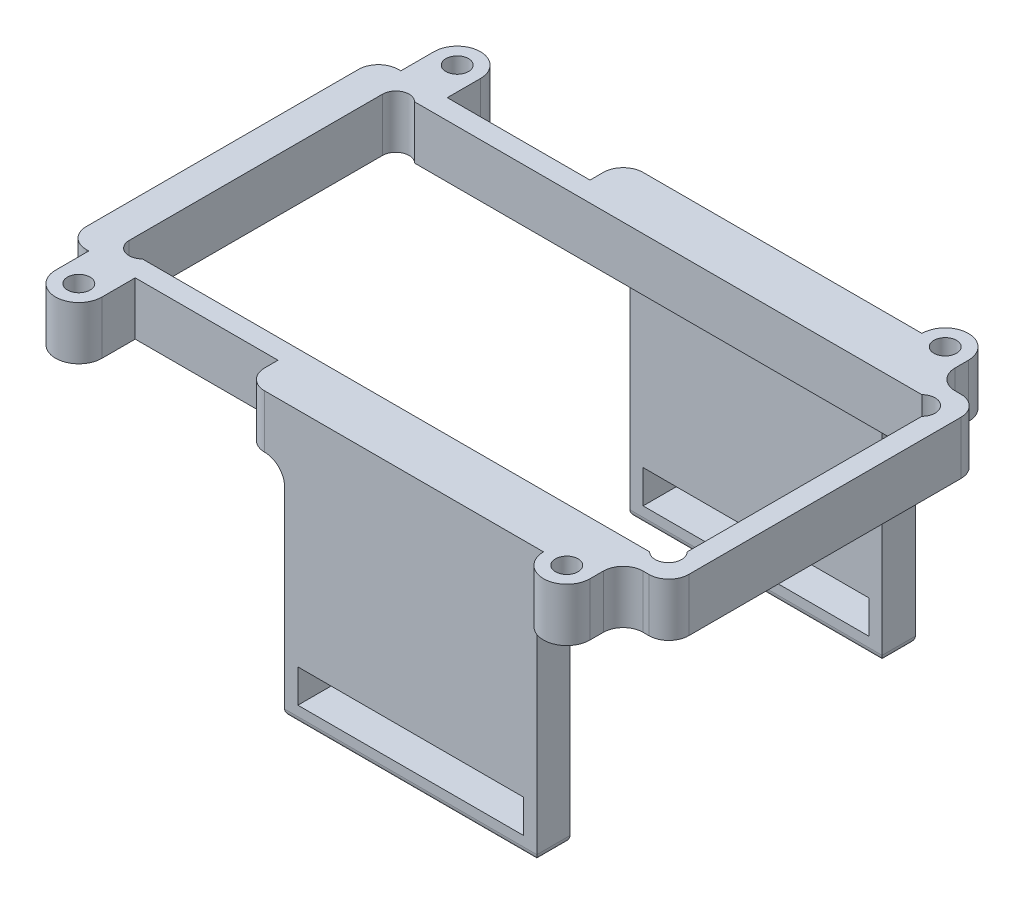
SolidWorks part; units mm, degrees
material "AISI 1035 钢 (SS)"
ref_plane "前视基准面" through (0, 0, 0) normal (0, 0, 1) x (1, 0, 0)
ref_plane "上视基准面" through (0, 0, 0) normal (0, 1, 0) x (1, 0, 0)
ref_plane "右视基准面" through (0, 0, 0) normal (1, 0, 0) x (0, 0, -1)
sketch "草图1" plane through (0, 0, 0) normal (0, 1, 0) x (1, 0, 0)
  line L0 (-34.1716, -20.5) -> (36, -20.5)
  line L1 (-38, 23.5) -> (40, 23.5)
  line L2 (-40, 21.5) -> (-40, -21.5)
  line L3 (-38, -23.5) -> (40, -23.5)
  line L4 (40, 23.5) -> (40, -23.5)
  line L5 (-40, 23.5) -> (40, -23.5) construction
  line L6 (-40, -23.5) -> (40, 23.5) construction
  line L7 (-37, -20.5) -> (37, -20.5) construction
  line L8 (-34.1716, 20.5) -> (36, 20.5)
  line L9 (-37, 17.6716) -> (-37, -17.6716)
  line L10 (37, 20.5) -> (37, -20.5) construction
  line L11 (-6.6939, 3.9327) -> (38, -20.5) construction
  line L12 (-6.6939, -3.9327) -> (0.5, 0) construction
  line L13 (38, -18.5) -> (38, 18.5)
  line L14 (-37, 20.5) -> (37, 20.5) construction
  line L15 (-37, -20.5) -> (-35.5858, -19.0858) construction
  line L16 (0, 0) -> (-3.1731, 0) construction
  line L17 (-37, 20.5) -> (-37, -20.5) construction
  line L18 (-40, -23.5) -> (40, -23.5) construction
  line L19 (-40, 23.5) -> (-40, -23.5) construction
  line L20 (-40, 23.5) -> (40, 23.5) construction
  arc A0 (36, -20.5) -> (38, -18.5) centre (36, -18.5) ccw
  arc A1 (38, 18.5) -> (36, 20.5) centre (36, 18.5) ccw
  arc A2 (-37, -17.6716) -> (-34.1716, -20.5) centre (-35.5858, -19.0858) ccw
  arc A3 (-37, 17.6716) -> (-34.1716, 20.5) centre (-35.5858, 19.0858) cw
  arc A4 (-38, -23.5) -> (-40, -21.5) centre (-38, -21.5) cw
  arc A5 (-38, 23.5) -> (-40, 21.5) centre (-38, 21.5) ccw
  point P0 (0, 0)
  point P16 (38, 20.5)
  dimension "D5" = 2
  dimension "D8" = 4
  dimension "D9" = 2
  dimension "D1" = 80
  dimension "D2" = 47
  dimension "D4" = 2
  dimension "D6" = 45
  dimension "D7" = 2
  dimension "D3" = 3
extrude "凸台-拉伸1" add sketch "草图1" along normal blind 23.5
sketch "草图2" plane through (0, 0, 0) normal (0, -1, 0) x (1, 0, 0)
  line L0 (1, 23.5) -> (1, -23.5) construction
  line L1 (-38, 23.5) -> (40, 23.5) construction
  line L2 (40, -23.5) -> (-38, -23.5) construction
  line L3 (37.75, 0) -> (-35.75, 0) construction
  line L4 (37.75, 28.5) -> (37.75, -28.5) construction
  line L5 (40, 0) -> (55, 0) construction
  line L6 (40, 23.5) -> (40, -23.5) construction
  line L7 (55, 0) -> (-46, 0) construction
  line L9 (48.125, 23.5) -> (41.25, 23.5)
  line L11 (-42.625, -23.5) -> (-39.25, -23.5)
  line L13 (-34.1716, 20.5) -> (36, 20.5) construction
  line L14 (5.4444, -0.4555) -> (5.4444, 0.4555) construction
  line L15 (-34.1716, 20.5) -> (42.2319, 20.5)
  line L16 (34.25, 23.5) -> (-32.25, 23.5)
  line L17 (42.2319, -20.5) -> (-34.1716, -20.5)
  line L18 (47, -20.5) -> (-38, 20.5) construction
  line L19 (47, 20.5) -> (-38, -20.5) construction
  line L20 (37.75, 18.5) -> (37.75, 28.5) construction
  line L21 (34.25, 23.5) -> (34.25, 28.5)
  line L22 (41.25, -23.5) -> (41.25, -28.5)
  line L23 (41.25, 23.5) -> (41.25, 28.5)
  line L24 (34.25, -23.5) -> (34.25, -28.5)
  line L25 (-32.25, -23.5) -> (-32.25, -28.5)
  line L26 (-39.25, -23.5) -> (-39.25, -28.5)
  line L27 (-39.25, 23.5) -> (-39.25, 28.5)
  line L28 (-32.25, 23.5) -> (-32.25, 28.5)
  line L29 (-37, -17.6716) -> (-37, 17.6716)
  line L30 (45.0603, -14.2439) -> (-37, -14.2439) construction
  line L31 (4.0302, -14.2439) -> (4.0302, -22.3158) construction
  line L32 (45.0603, 17.6716) -> (45.0603, -17.6716)
  line L33 (41.25, -23.5) -> (48.125, -23.5)
  line L34 (-32.25, -23.5) -> (34.25, -23.5)
  line L35 (-39.25, 23.5) -> (-42.625, 23.5)
  line L36 (-42.625, 23.5) -> (-42.625, -23.5)
  line L37 (48.125, 23.5) -> (48.125, -23.5)
  circle A0 centre (37.75, 28.5) radius 1.7
  arc A1 (41.25, -28.5) -> (34.25, -28.5) centre (37.75, -28.5) cw
  arc A2 (41.25, 28.5) -> (34.25, 28.5) centre (37.75, 28.5) ccw
  circle A3 centre (37.75, -28.5) radius 1.7
  arc A4 (-39.25, -28.5) -> (-32.25, -28.5) centre (-35.75, -28.5) ccw
  circle A5 centre (-35.75, -28.5) radius 1.7
  arc A6 (-39.25, 28.5) -> (-32.25, 28.5) centre (-35.75, 28.5) cw
  circle A7 centre (-35.75, 28.5) radius 1.7
  arc A8 (-37, -17.6716) -> (-34.1716, -20.5) centre (-35.5858, -19.0858) ccw construction
  arc A9 (-34.1716, 20.5) -> (-37, 17.6716) centre (-35.5858, 19.0858) ccw construction
  arc A10 (-37, -17.6716) -> (-34.1716, -20.5) centre (-35.5858, -19.0858) ccw
  arc A11 (-34.1716, 20.5) -> (-37, 17.6716) centre (-35.5858, 19.0858) ccw
  arc A12 (42.2319, 20.5) -> (45.0603, 17.6716) centre (43.6461, 19.0858) cw
  arc A13 (45.0603, -17.6716) -> (42.2319, -20.5) centre (43.6461, -19.0858) cw
  point P6 (1, 0)
  point P18 (4.5, 0)
  point P31 (37.75, 23.5)
  dimension "D3" = 3.4
  dimension "D1" = 73.5
  dimension "D2" = 57
  dimension "D4" = 15
  dimension "D5" = 101
  dimension "D6" = 85
extrude "凸台-拉伸2" add sketch "草图2" along normal blind 8
sketch "草图4" plane through (-40, 0, 0) normal (-1, 0, 0) x (0, 0, 1)
  line L0 (0, 0) -> (0, 20.5) construction
  line L3 (-21.5, 0) -> (21.5, 0) construction
  line L4 (-21.5, 23.5) -> (21.5, 23.5) construction
  line L6 (17, 0) -> (-17, 0)
  line L7 (20, 3) -> (20, 17.5)
  line L8 (17, 20.5) -> (-17, 20.5)
  line L9 (-20, 3) -> (-20, 17.5)
  line L10 (20, 0) -> (-20, 20.5) construction
  line L11 (20, 20.5) -> (-20, 0) construction
  arc A0 (-17, 0) -> (-20, 3) centre (-17, 3) cw
  arc A1 (-20, 17.5) -> (-17, 20.5) centre (-17, 17.5) cw
  arc A2 (17, 20.5) -> (20, 17.5) centre (17, 17.5) cw
  arc A3 (17, 0) -> (20, 3) centre (17, 3) ccw
  point P6 (0, 11.75)
  point P7 (0, 10.25)
  dimension "D3" = 3
  dimension "D1" = 3
  dimension "D2" = 40
extrude "切除-拉伸1" cut sketch "草图4" against normal up to next
sketch "草图5" plane through (0, 0, -23.5) normal (0, 0, -1) x (-1, 0, 0)
  line L0 (-1, 23.5) -> (-1, 19.5) construction
  line L1 (-40, 23.5) -> (38, 23.5) construction
  line L2 (-40, 11.75) -> (-37, 11.75) construction
  line L3 (-40, 23.5) -> (-40, 0) construction
  line L4 (-37, 11.75) -> (-37, 17.5)
  line L5 (-35, 19.5) -> (33, 19.5)
  line L6 (38, 23.5) -> (38, 0) construction
  line L7 (-37, 11.75) -> (-37, 6)
  line L8 (-35, 4) -> (33, 4)
  line L9 (35, 6) -> (35, 17.5)
  arc A0 (-37, 6) -> (-35, 4) centre (-35, 6) ccw
  arc A1 (-37, 17.5) -> (-35, 19.5) centre (-35, 17.5) cw
  arc A2 (33, 19.5) -> (35, 17.5) centre (33, 17.5) cw
  arc A3 (33, 4) -> (35, 6) centre (33, 6) ccw
  point P16 (-37, 4)
  point P21 (35, 19.5)
  dimension "D5" = 2
  dimension "D1" = 4
  dimension "D2" = 3
  dimension "D3" = 3
  dimension "D4" = 7.75
extrude "切除-拉伸2" cut sketch "草图5" against normal up to surface (47 mm away) up to face at (1, 3.875, 23.5)
sketch "草图6" plane through (40, 0, 0) normal (1, 0, 0) x (0, 0, -1)
  line L0 (0, 23.5) -> (0, 20.5) construction
  line L1 (-23.5, 23.5) -> (23.5, 23.5) construction
  line L2 (23.5, 11.75) -> (21, 11.75) construction
  line L3 (23.5, 23.5) -> (23.5, 0) construction
  line L4 (21, 5) -> (21, 18.5)
  line L5 (19, 20.5) -> (-19, 20.5)
  line L6 (0, 20.5) -> (0, 7.2335) construction
  line L7 (-21, 5) -> (-21, 18.5)
  line L9 (0, 3) -> (0, 0) construction
  line L10 (-20.5, 0) -> (20.5, 0) construction
  line L13 (16, 0) -> (-16, 0)
  line L15 (-21, 5) -> (-21, 0)
  line L16 (-23.5, 0) -> (-20.5, 0) construction
  line L17 (-21, 0) -> (-16, 0)
  line L18 (21, 5) -> (21, 0)
  line L19 (23.5, 0) -> (20.5, 0) construction
  line L20 (21, 0) -> (16, 0)
  arc A0 (-21, 18.5) -> (-19, 20.5) centre (-19, 18.5) cw
  arc A1 (19, 20.5) -> (21, 18.5) centre (19, 18.5) cw
  point P14 (-21, 11.75)
  point P17 (-21, 20.5)
  point P20 (21, 20.5)
  point P23 (-21, 3)
  point P26 (21, 3)
  point P37 (-16, 3)
  dimension "D3" = 2
  dimension "D1" = 3
  dimension "D2" = 2.5
extrude "切除-拉伸3" cut sketch "草图6" against normal up to next
sketch "草图9" plane through (0, 0, 23.5) normal (0, 0, 1) x (1, 0, 0)
  line L0 (34.25, -8) -> (34.25, 0)
  line L1 (34.25, 0) -> (-10.75, 0)
  line L2 (-10.75, 0) -> (-10.75, -8)
  line L3 (34.25, -8) -> (-32.25, -8) construction
  line L4 (-10.75, -8) -> (34.25, -8)
  dimension "D1" = 45
extrude "凸台-拉伸3" add sketch "草图9" along normal blind 5
sketch "草图10" plane through (0, 0, -23.5) normal (0, 0, -1) x (-1, 0, 0)
  line L0 (-34.25, -8) -> (10.75, -8)
  line L1 (32.25, -8) -> (-34.25, -8) construction
  line L2 (-34.25, -8) -> (-34.25, 0)
  line L3 (-34.25, 0) -> (10.75, 0)
  line L4 (10.75, 0) -> (10.75, -8)
  dimension "D1" = 45
extrude "凸台-拉伸4" add sketch "草图10" along normal blind 5
sketch "草图11" plane through (0, -8, 0) normal (0, -1, 0) x (1, 0, 0)
  line L0 (-10.75, 28.5) -> (34.25, 28.5) construction
  line L1 (-4.75, 28.5) -> (33.25, 28.5)
  line L2 (-4.75, 28.5) -> (-4.75, 23.5)
  line L3 (-4.75, 23.5) -> (33.25, 23.5)
  line L4 (33.25, 28.5) -> (33.25, 23.5)
  line L5 (-10.75, 28.5) -> (-10.75, 23.5) construction
  dimension "D1" = 5
  dimension "D2" = 38
  dimension "D3" = 6
extrude "凸台-拉伸5" add sketch "草图11" along normal blind 33
sketch "草图12" plane through (0, 0, 23.5) normal (0, 0, -1) x (-1, 0, 0)
  line L0 (4.75, -41) -> (-33.25, -41) construction
  line L1 (-31.25, -38.5) -> (2.75, -38.5)
  line L2 (-31.25, -38.5) -> (-31.25, -33.5)
  line L3 (-31.25, -33.5) -> (2.75, -33.5)
  line L4 (2.75, -38.5) -> (2.75, -33.5)
  line L5 (-31.25, -38.5) -> (2.75, -33.5) construction
  line L6 (-31.25, -33.5) -> (2.75, -38.5) construction
  line L7 (-33.25, -41) -> (-33.25, -8) construction
  point P0 (-14.25, -36)
  dimension "D1" = 5
  dimension "D2" = 5
  dimension "D3" = 34
  dimension "D4" = 2
extrude "切除-拉伸4" cut sketch "草图12" against normal blind 5
mirror "镜向1" about plane through (0, 0, 0) normal (0, 0, 1) of "切除-拉伸4", "凸台-拉伸5"
sketch "草图13" plane through (0, 23.5, 0) normal (0, 1, 0) x (1, 0, 0)
  line L0 (-38, 23.5) -> (40, 23.5)
  line L1 (40, 23.5) -> (40, -23.5)
  line L2 (40, -23.5) -> (-38, -23.5)
  line L3 (38, 18.5) -> (38, -18.5)
  line L4 (-40, -21.5) -> (-40, 21.5)
  line L5 (-34.1716, 20.5) -> (36, 20.5)
  line L6 (-37, 17.6716) -> (-37, -17.6716)
  line L7 (-34.1716, -20.5) -> (36, -20.5)
  arc A0 (-40, 21.5) -> (-38, 23.5) centre (-38, 21.5) cw
  arc A1 (-40, -21.5) -> (-38, -23.5) centre (-38, -21.5) ccw
  arc A2 (38, 18.5) -> (36, 20.5) centre (36, 18.5) ccw
  arc A3 (36, -20.5) -> (38, -18.5) centre (36, -18.5) ccw
  arc A4 (-37, -17.6716) -> (-34.1716, -20.5) centre (-35.5858, -19.0858) ccw
  arc A6 (-34.1716, 20.5) -> (-37, 17.6716) centre (-35.5858, 19.0858) ccw
extrude "切除-拉伸5" cut sketch "草图13" against normal blind 23.5
sketch "草图14" plane through (0, -8, 0) normal (0, -1, 0) x (1, 0, 0)
  line L0 (-37.5858, 19.0858) -> (-37.5858, -19.0858)
  line L1 (-37, 17.6716) -> (-37, -17.6716)
  arc A0 (-34.1716, 20.5) -> (-37, 17.6716) centre (-35.5858, 19.0858) ccw construction
  arc A1 (-37, -17.6716) -> (-34.1716, -20.5) centre (-35.5858, -19.0858) ccw construction
  arc A2 (-37, -17.6716) -> (-37.5858, -19.0858) centre (-35.5858, -19.0858) ccw
  arc A3 (-37.5858, 19.0858) -> (-37, 17.6716) centre (-35.5858, 19.0858) ccw
extrude "切除-拉伸6" cut sketch "草图14" against normal through all
fillet "圆角1" radius 3 10 edges at (-10.75, -4, 28.5) (-10.75, -4, -28.5) (-42.625, -4, 23.5) (-42.625, -4, -23.5) (-4.75, -8, 26) (-4.75, -8, -26) (41.25, -4, 23.5) (41.25, -4, -23.5) (48.125, -4, 23.5) (48.125, -4, -23.5)
fillet "圆角2" radius 1 2 edges at (33.25, -8, 26) (33.25, -8, -26)
fillet "圆角3" radius 1 8 edges at (33.25, -41, 26) (-4.75, -41, 26) (-4.75, -41, -26) (33.25, -41, -26) (14.25, -41, 23.5) (14.25, -41, 28.5) (14.25, -41, -28.5) (14.25, -41, -23.5)
